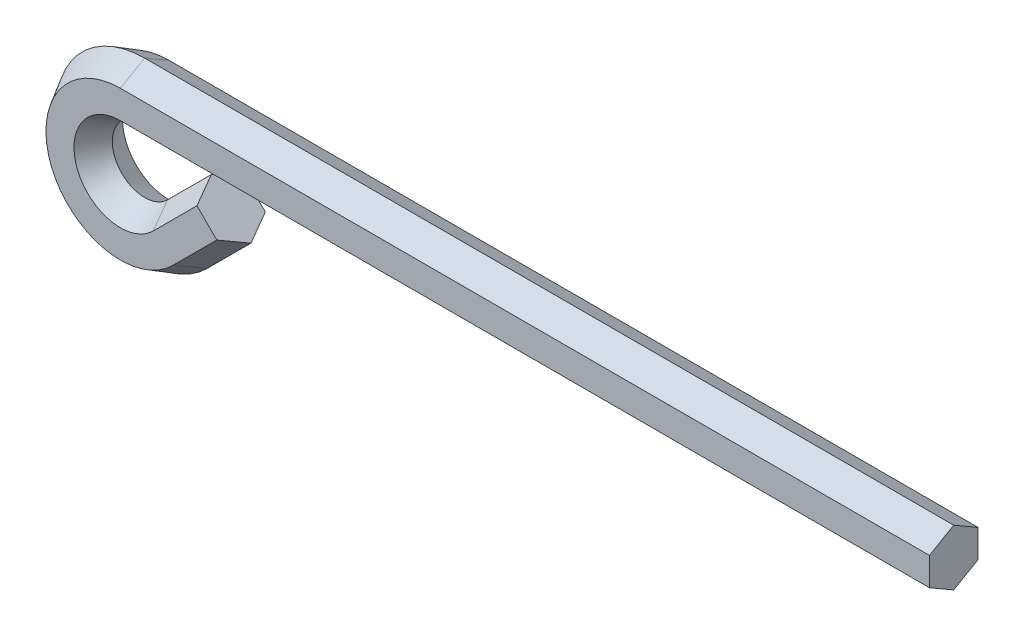
SolidWorks part; units mm, degrees
material "PW20:29:Sc:0:"
ref_plane "Front" through (0, 0, 0) normal (0, 0, 1) x (1, 0, 0)
ref_plane "Top" through (0, 0, 0) normal (0, 1, 0) x (1, 0, 0)
ref_plane "Right" through (0, 0, 0) normal (1, 0, 0) x (0, 0, -1)
other "LENGTH"
sketch "Sketch1" plane through (0, 0, 0) normal (0, 0, 1) x (1, 0, 0)
  line L0 (100, 4) -> (0, 4)
  line L1 (2.8284, -2.8284) -> (8.2426, 2.5858)
  line L2 (8.2426, 2.5858) -> (9.6569, 4) construction
  arc A0 (0, 4) -> (2.8284, -2.8284) centre (0, 0) ccw
  dimension "Center_Rad" = 4
  dimension "Length" = 100
  dimension "Overlap" = 2
  dimension "Angle" = 45
ref_plane "Plane4" through (100, 4, 0) normal (-1, 0, 0) x (0, 0, 1)
sketch "Sketch2" plane through (100, 4, 0) normal (-1, 0, 0) x (0, 0, 1)
  line L0 (0, 0) -> (0, 6.9282) construction
  line L1 (-3, 5.1962) -> (0, 6.9282)
  line L2 (-3, 1.7321) -> (-3, 5.1962)
  line L3 (0, 0) -> (3, 1.7321)
  line L4 (3, 1.7321) -> (3, 5.1962)
  line L5 (3, 5.1962) -> (0, 6.9282)
  line L6 (0, 0) -> (-3, 1.7321)
  line L7 (3, 1.7321) -> (-3, 5.1962) construction
  line L8 (3, 5.1962) -> (-3, 1.7321) construction
  dimension "Hex_Diam" = 6
sweep "Base-Sweep" add profiles "Sketch2" path "Sketch1"
ref_axis "center_axis" [suppressed] through (0, 0, 53) along (0, 0, -1)
